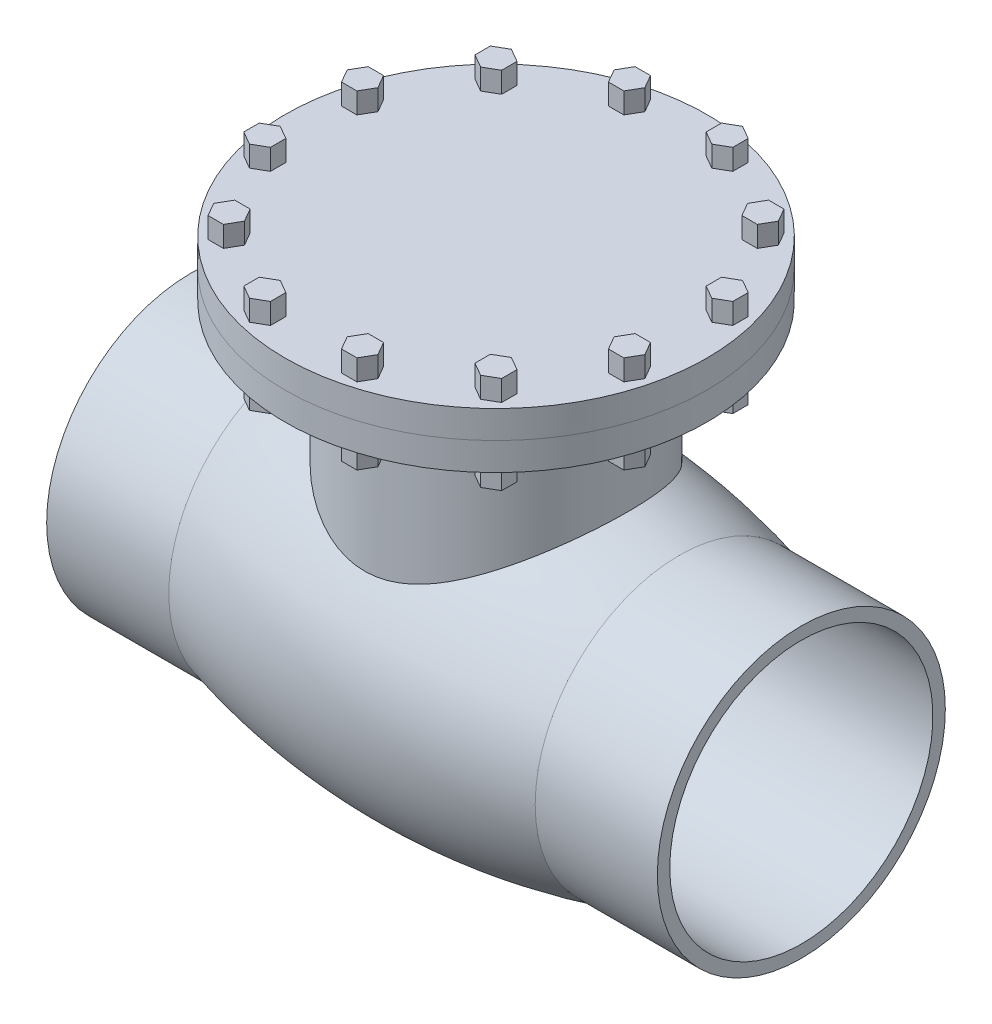
SolidWorks part; units mm, degrees
ref_plane "Front Plane" through (0, 0, 0) normal (0, 0, 1) x (1, 0, 0)
ref_plane "Top Plane" through (0, 0, 0) normal (0, 1, 0) x (1, 0, 0)
ref_plane "Right Plane" through (0, 0, 0) normal (1, 0, 0) x (0, 0, -1)
sketch "Flow Extrude Sketch" plane through (0, 0, 0) normal (0, 0, 1) x (1, 0, 0)
  line L0 (-245.3211, 0) -> (110.5039, 0) construction
  line L1 (0, 0) -> (0, 85.3189) construction
  line L2 (209.55, 164.719) -> (349.25, 164.719)
  line L3 (-349.25, 164.719) -> (-209.55, 164.719)
  line L4 (-349.25, 164.719) -> (-349.25, 0)
  line L5 (-349.25, 0) -> (349.25, 0)
  line L6 (349.25, 164.719) -> (349.25, 0)
  arc A1 (-209.55, 164.719) -> (209.55, 164.719) centre (0, -623.8183) cw
  point P13 (0, 192.0875)
  dimension "A" = 329.438
  dimension "B" = 698.5
  dimension "B*.6" = 419.1
  dimension "B*.55" = 384.175
revolve "Flow Extrude" add sketch "Flow Extrude Sketch" angle 360 about L0
sketch "Body Extrude Sketch" plane through (0, 0, 0) normal (0, 1, 0) x (1, 0, 0)
  line L1 (0, -96.6135) -> (0, 96.6135) construction
  circle A0 centre (0, 0) radius 150.4
  dimension "H*.8" = 300.8
extrude "Body Extrude" add sketch "Body Extrude Sketch" along normal blind 376
sketch "Flange Bottom Sketch" plane through (0, 376, 0) normal (0, 1, 0) x (-1, 0, 0)
  circle A0 centre (0, 0) radius 241.3
  dimension "O" = 482.6
extrude "Flange Bottom" add sketch "Flange Bottom Sketch" against normal blind 31.75
sketch "Flange Top Sketch" plane through (0, 344.25, 0) normal (0, -1, 0) x (1, 0, 0)
  circle A1 centre (0, 0) radius 241.3
  circle A2 centre (0, 0) radius 241.3
  dimension "D1" = 0
extrude "Flange Top" add sketch "Flange Top Sketch" along normal blind 31.75
sketch "ID Sketch" plane through (349.25, 0, 0) normal (-1, 0, 0) x (0, 0, 1)
  circle A0 centre (0, 0) radius 150.495
  dimension "A-2*t" = 300.99
extrude "ID Cut" cut sketch "ID Sketch" along normal through all
ref_plane "Bolt Plane" through (0, 399.8125, 0) normal (0, 1, 0) x (-1, 0, 0)
sketch "Bolt Sketch" plane through (0, 399.8125, 0) normal (0, 1, 0) x (-1, 0, 0)
  line L0 (0, 0) -> (-133.115, -35.668) construction
  line L1 (0, 0) -> (-142.2485, 0) construction
  line L2 (-208.5434, -38.2814) -> (-223.7834, -47.0802)
  line L3 (-223.7834, -47.0802) -> (-223.7834, -64.6778)
  line L4 (-223.7834, -64.6778) -> (-208.5434, -73.4767)
  line L5 (-208.5434, -73.4767) -> (-193.3034, -64.6778)
  line L6 (-193.3034, -64.6778) -> (-193.3034, -47.0802)
  line L7 (-193.3034, -47.0802) -> (-208.5434, -38.2814)
  circle A0 centre (0, 0) radius 215.9 construction
  circle A2 centre (-208.5434, -55.879) radius 15.24 construction
  dimension "BC" = 431.8
  dimension "DH*1.2" = 30.48
  dimension "Angle" = 15
extrude "Bolt" add sketch "Bolt Sketch" against normal blind 111.125
pattern_circular "Bolt Pattern" count 12 every 30 about axis through (0, 344.25, 0) along (0, 1, 0) of "Bolt"
sketch "Sketch1" plane through (0, 0, 0) normal (0, 0, 1) x (1, 0, 0)
  line L1 (-241.3, 344.25) -> (241.3, 344.25)
  line L2 (-241.3, 344.25) -> (241.3, 344.25)
  dimension "D1" = 0
split line "Split Line1"
sketch "CPointSketch" plane through (0, 0, 0) normal (0, 0, 1) x (1, 0, 0)
  line L2 (349.25, -164.719) -> (349.25, 164.719) construction
  line L3 (-349.25, 164.719) -> (-349.25, -164.719) construction
  point P0 (-349.25, 0)
  point P1 (349.25, 0)
  point P4 (0, 0)
other "CPoint1" parameters "Diameter"=304.8, "StubLength"=0
ref_axis "Axis1" through (359.25, 0, 0) along (-1, 0, 0)
other "CPoint2" parameters "Diameter"=304.8, "StubLength"=0
ref_axis "Axis2" through (-359.25, 0, 0) along (1, 0, 0)
other "RPoint1"
